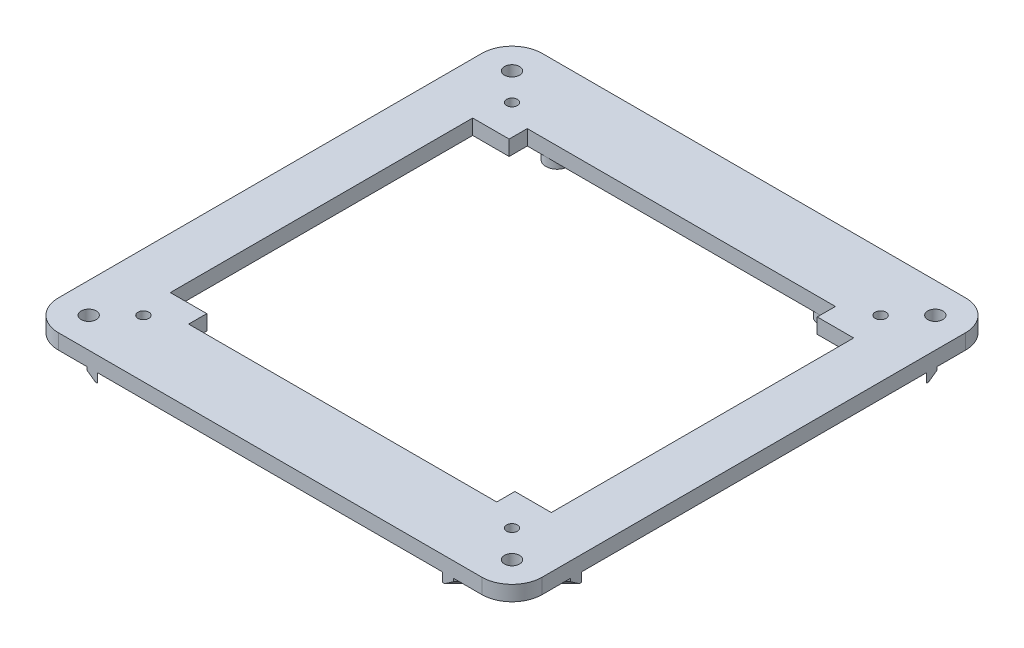
SolidWorks part; units mm, degrees
ref_plane "Front Plane" through (0, 0, 0) normal (0, 0, 1) x (1, 0, 0)
ref_plane "Top Plane" through (0, 0, 0) normal (0, 1, 0) x (1, 0, 0)
ref_plane "Right Plane" through (0, 0, 0) normal (1, 0, 0) x (0, 0, -1)
sketch "Sketch1" plane through (0, 0, 0) normal (0, 1, 0) x (1, 0, 0)
  line L0 (0, 0) -> (0, 25.4)
  line L1 (12.7, 38.1) -> (190.5, 38.1)
  line L2 (203.2, 25.4) -> (203.2, -152.4)
  line L3 (190.5, -165.1) -> (12.7, -165.1)
  line L4 (0, -152.4) -> (0, -127)
  line L5 (21.59, -127) -> (181.61, -127)
  line L6 (181.61, -127) -> (181.61, 0)
  line L7 (181.61, 0) -> (21.59, 0)
  line L10 (0, 0) -> (0, -127)
  line L12 (21.59, 0) -> (21.59, -127)
  arc A0 (12.7, -165.1) -> (0, -152.4) centre (12.7, -152.4) cw
  arc A1 (203.2, -152.4) -> (190.5, -165.1) centre (190.5, -152.4) cw
  arc A2 (190.5, 38.1) -> (203.2, 25.4) centre (190.5, 25.4) cw
  arc A3 (0, 25.4) -> (12.7, 38.1) centre (12.7, 25.4) cw
  point P13 (203.2, -165.1)
  point P16 (203.2, 38.1)
  point P19 (0, 38.1)
  dimension "D6" = 12.7
  dimension "D1" = 203.2
  dimension "D2" = 38.1
  dimension "D3" = 203.2
  dimension "D4" = 21.59
  dimension "D5" = 127
  dimension "D7" = 21.59
extrude "Boss-Extrude2" add sketch "Sketch1" along normal blind 6.35
sketch "Sketch2" plane through (0, 6.35, 0) normal (0, 1, 0) x (1, 0, 0)
  circle A0 centre (12.7, 25.4) radius 3.175
  circle A1 centre (190.5, 25.4) radius 3.175
  circle A2 centre (190.5, -152.4) radius 3.175
  circle A3 centre (12.7, -152.4) radius 3.175
  arc A4 (12.7, 38.1) -> (0, 25.4) centre (12.7, 25.4) ccw construction
  dimension "D1" = 6.35
extrude "Cut-Extrude1" cut sketch "Sketch2" against normal through all
sketch "Sketch8" plane through (0, 0, 0) normal (0, -1, 0) x (-1, 0, 0)
  line L0 (-3.7197, -161.3803) -> (-199.4803, 34.3803) construction
  line L1 (-24.1978, 13.9022) -> (-24.1978, 38.1) construction
  line L2 (-190.5, 38.1) -> (-12.7, 38.1) construction
  line L3 (-24.1978, 13.9022) -> (0, 13.9022) construction
  line L5 (-24.1978, 13.9022) -> (-3.7197, 34.3803) construction
  line L6 (0, 25.4) -> (0, -152.4) construction
  arc A0 (0, 25.4) -> (-12.7, 38.1) centre (-12.7, 25.4) ccw construction
  circle A1 centre (-24.1978, 13.9022) radius 2.286
  arc A2 (-12.7, -165.1) -> (0, -152.4) centre (-12.7, -152.4) ccw construction
  arc A3 (-190.5, 38.1) -> (-203.2, 25.4) centre (-190.5, 25.4) ccw construction
  circle A4 centre (-24.1978, -140.9022) radius 2.286
  circle A5 centre (-179.0022, -140.9022) radius 2.286
  circle A6 centre (-179.0022, 13.9022) radius 2.286
  point P8 (-101.6, -63.5)
  dimension "D2" = 4.572
  dimension "D1" = 28.9603
  dimension "D3" = 4
extrude "Cut-Extrude4" cut sketch "Sketch8" against normal through all
sketch "Sketch9" plane through (0, 6.35, 0) normal (0, 1, 0) x (1, 0, 0)
  line L0 (21.59, 0) -> (181.61, 0) construction
  line L1 (36.8978, 0) -> (166.3022, 0)
  line L2 (36.8978, 0) -> (36.8978, 7.62)
  line L3 (36.8978, 7.62) -> (166.3022, 7.62)
  line L4 (166.3022, 0) -> (166.3022, 7.62)
  line L5 (181.61, -127) -> (21.59, -127) construction
  line L6 (166.3022, -127) -> (36.8978, -127)
  line L7 (166.3022, -127) -> (166.3022, -134.62)
  line L8 (166.3022, -134.62) -> (36.8978, -134.62)
  line L9 (36.8978, -127) -> (36.8978, -134.62)
  line L10 (12.7, -165.1) -> (190.5, -165.1) construction
  line L11 (190.5, 38.1) -> (12.7, 38.1) construction
  circle A0 centre (179.0022, 13.9022) radius 2.286 construction
  circle A1 centre (24.1978, 13.9022) radius 2.286 construction
  point P12 (101.6, -134.62)
  point P15 (101.6, -165.1)
  dimension "D1" = 12.7
  dimension "D2" = 12.7
  dimension "D3" = 30.48
extrude "Cut-Extrude5" cut sketch "Sketch9" against normal through all
sketch "Sketch10" plane through (0, 0, 0) normal (0, -1, 0) x (-1, 0, 0)
  line L0 (-203.2, -152.4) -> (-203.2, 25.4) construction
  line L1 (-12.7, -165.1) -> (-190.5, -165.1) construction
  line L2 (-190.5, 38.1) -> (-12.7, 38.1) construction
  line L3 (0, 25.4) -> (0, -152.4) construction
  circle A0 centre (-44.45, -139.7) radius 2.286
  circle A1 centre (-158.75, -139.7) radius 2.286
  circle A2 centre (-158.75, 12.7) radius 2.286
  circle A3 centre (-44.45, 12.7) radius 2.286
  circle A4 centre (-44.45, 12.7) radius 4.826
  circle A5 centre (-158.75, 12.7) radius 4.826
  circle A6 centre (-158.75, -139.7) radius 4.826
  circle A7 centre (-44.45, -139.7) radius 4.826
  point P10 (0, 0)
  point P11 (0, 0)
  point P12 (0, 0)
  dimension "D1" = 4.572
  dimension "D2" = 44.45
  dimension "D3" = 25.4
  dimension "D4" = 25.4
  dimension "D5" = 44.45
  dimension "D6" = 2.54
extrude "Boss-Extrude3" add sketch "Sketch10" along normal blind 3.81
sketch "Sketch11" plane through (0, 0, 0) normal (0, -1, 0) x (1, 0, 0)
  line L0 (174.0713, -38.1) -> (187.3849, -24.7864)
  line L1 (190.5, -38.1) -> (12.7, -38.1) construction
  line L2 (203.2, 152.4) -> (203.2, -25.4) construction
  line L3 (203.2, -8.9713) -> (203.2, -13.4614)
  line L4 (203.2, -13.4614) -> (193.0933, -23.5682)
  line L5 (178.5614, -38.1) -> (174.0713, -38.1)
  line L6 (189.8864, -22.2849) -> (203.2, -8.9713)
  line L7 (188.6682, -27.9933) -> (178.5614, -38.1)
  line L8 (3.7197, -34.3803) -> (199.4803, 161.3803) construction
  line L9 (10.1067, -23.5682) -> (0, -13.4614)
  line L10 (0, -8.9713) -> (13.3136, -22.2849)
  line L11 (0, -13.4614) -> (0, -8.9713)
  line L12 (15.8151, -24.7864) -> (29.1287, -38.1)
  line L13 (24.6386, -38.1) -> (14.5318, -27.9933)
  line L14 (29.1287, -38.1) -> (24.6386, -38.1)
  line L15 (14.5318, 154.9933) -> (24.6386, 165.1)
  line L16 (29.1287, 165.1) -> (15.8151, 151.7864)
  line L17 (24.6386, 165.1) -> (29.1287, 165.1)
  line L18 (13.3136, 149.2849) -> (0, 135.9713)
  line L19 (0, 140.4614) -> (10.1067, 150.5682)
  line L20 (0, 135.9713) -> (0, 140.4614)
  line L21 (193.0933, 150.5682) -> (203.2, 140.4614)
  line L22 (203.2, 135.9713) -> (189.8864, 149.2849)
  line L23 (203.2, 140.4614) -> (203.2, 135.9713)
  line L24 (187.3849, 151.7864) -> (174.0713, 165.1)
  line L25 (178.5614, 165.1) -> (188.6682, 154.9933)
  line L26 (174.0713, 165.1) -> (178.5614, 165.1)
  arc A0 (187.3849, -24.7864) -> (188.6682, -27.9933) centre (190.5, -25.4) ccw
  arc A1 (193.0933, -23.5682) -> (189.8864, -22.2849) centre (190.5, -25.4) ccw
  arc A2 (0, -25.4) -> (12.7, -38.1) centre (12.7, -25.4) ccw construction
  arc A3 (203.2, 152.4) -> (190.5, 165.1) centre (190.5, 152.4) ccw construction
  arc A4 (13.3136, -22.2849) -> (10.1067, -23.5682) centre (12.7, -25.4) ccw
  arc A5 (14.5318, -27.9933) -> (15.8151, -24.7864) centre (12.7, -25.4) ccw
  arc A6 (15.8151, 151.7864) -> (14.5318, 154.9933) centre (12.7, 152.4) ccw
  arc A7 (10.1067, 150.5682) -> (13.3136, 149.2849) centre (12.7, 152.4) ccw
  arc A8 (189.8864, 149.2849) -> (193.0933, 150.5682) centre (190.5, 152.4) ccw
  arc A9 (188.6682, 154.9933) -> (187.3849, 151.7864) centre (190.5, 152.4) ccw
  point P22 (101.6, 63.5)
  dimension "D4" = 6.35
  dimension "D1" = 29.1287
  dimension "D2" = 29.1287
  dimension "D3" = 3.175
  dimension "D6" = 177.8
  dimension "D8" = 125.7236
  dimension "D5" = 4
extrude "Boss-Extrude4" add sketch "Sketch11" along normal blind 3.81
chamfer "Chamfer1" distance 2.54 angle 45 8 edges at (19.5852, -3.81, 160.0466) (5.0534, -3.81, 145.5148) (183.6148, -3.81, 160.0466) (198.1466, -3.81, 145.5148) (183.6148, -3.81, -33.0466) (198.1466, -3.81, -18.5148) (5.0534, -3.81, -18.5148) (19.5852, -3.81, -33.0466)
